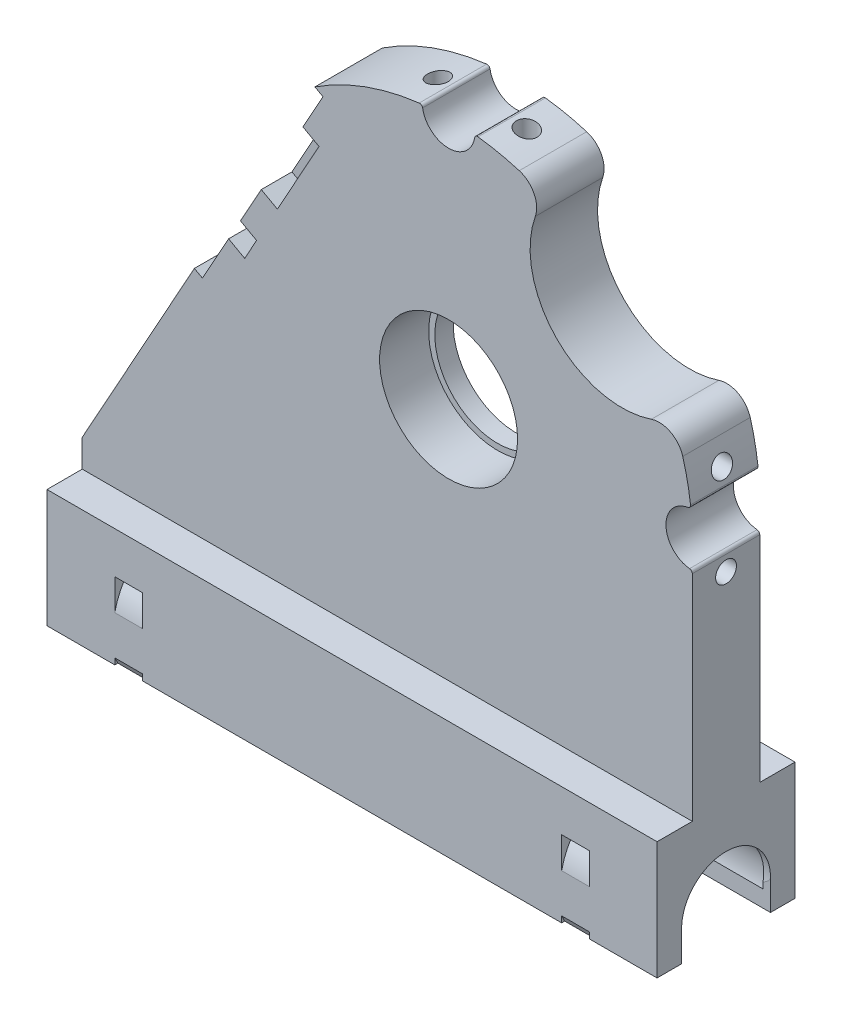
SolidWorks part; units mm, degrees
ref_plane "Alzado" through (0, 0, 0) normal (0, 0, 1) x (1, 0, 0)
ref_plane "Planta" through (0, 0, 0) normal (0, 1, 0) x (1, 0, 0)
ref_plane "Vista lateral" through (0, 0, 0) normal (1, 0, 0) x (0, 0, -1)
sketch "Croquis1" plane through (0, 0, 0) normal (0, 0, 1) x (1, 0, 0)
  line L1 (-25.8795, 44.4694) -> (-23.2553, 43.0157)
  line L2 (-23.2553, 43.0157) -> (-21.3161, 46.5141)
  line L3 (-21.3161, 46.5141) -> (-23.9399, 47.9686)
  line L5 (-20.5463, 54.0909) -> (-17.9224, 52.6365)
  line L6 (-17.9224, 52.6365) -> (-11.1351, 64.8812)
  line L7 (-11.1351, 64.8812) -> (-13.7589, 66.3356)
  line L8 (-11.7988, 72.9658) -> (-10.4868, 72.2386)
  line L17 (-10.4868, 72.2386) -> (-30.1459, 36.7728)
  line L18 (-30.1459, 36.7728) -> (-31.4578, 37.5)
  line L19 (-31.4578, 37.5) -> (-49.75, 4.5)
  line L20 (49.75, 0) -> (49.75, 34.9761)
  line L22 (-49.75, 4.5) -> (-49.75, 0)
  line L23 (-49.75, 0) -> (49.75, 0)
  line L25 (40.7, 29.375) -> (40.7, 35.625)
  line L26 (43.55, 29.375) -> (43.55, 35.625)
  line L27 (43.55, 29.375) -> (40.7, 29.375)
  line L28 (43.55, 35.625) -> (40.7, 35.625)
  line L29 (43.55, 43.875) -> (40.7, 43.875)
  line L30 (40.7, 50.125) -> (40.7, 43.875)
  line L31 (43.55, 50.125) -> (43.55, 43.875)
  line L32 (43.55, 50.125) -> (40.7, 50.125)
  line L33 (20.375, 70.44) -> (14.125, 70.44)
  line L34 (20.375, 70.44) -> (20.375, 73.29)
  line L35 (20.375, 73.29) -> (14.125, 73.29)
  line L36 (14.125, 70.44) -> (14.125, 73.29)
  line L37 (-0.375, 73.29) -> (-0.375, 70.44)
  line L38 (5.875, 70.44) -> (-0.375, 70.44)
  line L39 (5.875, 73.29) -> (5.875, 70.44)
  line L40 (5.875, 73.29) -> (-0.375, 73.29)
  arc A0 (49.4597, 44.5454) -> (14.7954, 79.2097) centre (10, 39.75) ccw
  arc A1 (14.7954, 79.2097) -> (14.2419, 78.7953) centre (14.7351, 78.7133) ccw
  arc A2 (5.7611, 78.7776) -> (14.2419, 78.7953) centre (10, 79.5) ccw
  arc A3 (5.7611, 78.7776) -> (5.2079, 79.19) centre (5.2682, 78.6936) ccw
  arc A4 (5.2079, 79.19) -> (-11.7988, 72.9658) centre (10, 39.75) ccw
  arc A5 (49.75, 34.9761) -> (49.3021, 35.4734) centre (49.25, 34.9761) ccw
  arc A6 (49.0453, 43.9919) -> (49.3021, 35.4734) centre (49.75, 39.75) ccw
  arc A7 (49.0453, 43.9919) -> (49.4597, 44.5454) centre (48.9633, 44.4851) ccw
  circle A8 centre (10, 39.75) radius 11.25
  circle A11 centre (10, 39.75) radius 10.25
  point P30 (10, 59.75)
  point P65 (5.875, 71.865)
  dimension "D2" = 22.5
  dimension "D7" = 4.3
  dimension "D8" = 0.5
  dimension "D9" = 0.5
  dimension "D10" = 39.75
  dimension "D11" = 4.3
  dimension "D25" = 0.5
  dimension "D26" = 0.5
  dimension "D36" = 20.5
  dimension "D37" = 40.55
  dimension "D4" = 6.25
  dimension "D5" = 2.85
  dimension "D6" = 2.85
  dimension "D12" = 39.75
  dimension "D13" = 10
  dimension "D14" = 99.5
  dimension "D15" = 33
  dimension "D16" = 61
  dimension "D17" = 1.5
  dimension "D18" = 90
  dimension "D19" = 4
  dimension "D20" = 3
  dimension "D21" = 8.8
  dimension "D22" = 7
  dimension "D23" = 14
  dimension "D24" = 1.5
  dimension "D27" = 39.75
  dimension "D29" = 8.25
  dimension "D30" = 8.25
  dimension "D31" = 33.54
  dimension "D32" = 4.125
  dimension "D33" = 30.7
  dimension "D34" = 4.125
  dimension "D35" = 39.75
  dimension "D38" = 33.2158
  dimension "D39" = 25.1312
  dimension "D40" = 31.3161
  dimension "D41" = 3.2657
extrude "Saliente-Extruir1" add sketch "Croquis1" against normal blind 11 contours L7 L17 L5 L6 | L3 L17 L1 L2 | A8 A11 | A6 A7 A0 A1 A2 A3 A4 L8 L17 L7 L6 L5 L3 L2 L1 L18 L19 L22 L23 L20 A5 A8 L33 L36 L35 L34 L28 L26 L27 L25 L32 L31 L29 L30 L40 L39 L38 L37 region at (-23.5978, 45.492, 0) region at (-25.1837, 42.63, 0) region at (-15.8407, 59.486, 0) region at (-0.9318, 39.75, 0)
extrude "Cortar-Extruir1" cut sketch "Croquis1<8>" against normal blind 8 contours A8
sketch "Croquis1<8>" plane through (0, 0, 0) normal (0, 0, 1) x (1, 0, 0) same geometry as "Croquis1"
extrude "Cortar-Extruir2" cut sketch "Croquis1<9>" against normal blind 5 contours L7 L17 L5 L6 | L3 L17 L1 L2 region at (-23.5978, 45.492, 0) region at (-15.8407, 59.486, 0)
sketch "Croquis1<9>" plane through (0, 0, 0) normal (0, 0, 1) x (1, 0, 0) same geometry as "Croquis1"
sketch "Croquis3" plane through (40.7, 0, 0) normal (1, 0, 0) x (0, 0, -1)
  line L0 (11, 50.125) -> (11, 43.875) construction
  line L2 (11, 44.5454) -> (0, 44.5454) construction
  line L4 (11, 29.375) -> (11, 35.625) construction
  circle A0 centre (5.5, 47) radius 1.7
  circle A1 centre (5.5, 32.5) radius 1.7
  point P6 (11, 47)
  point P11 (5.5, 44.5454)
  point P15 (11, 32.5)
  dimension "D1" = 3.4
  dimension "D2" = 3.4
extrude "Cortar-Extruir3" cut sketch "Croquis3" along normal through all and the other way blind 10.95 contours A0 | A1
sketch "Croquis4" plane through (0, 0, -11) normal (0, 0, -1) x (-1, 0, 0)
  line L0 (-49.75, 10) -> (49.75, 10)
  line L3 (49.75, 0) -> (-49.75, 0) construction
  line L11 (30.1459, 36.7728) -> (10.4868, 72.2386)
  line L12 (10.4868, 72.2386) -> (11.7988, 72.9658)
  line L13 (-49.75, 34.9761) -> (-49.75, 0)
  line L14 (-49.75, 0) -> (49.75, 0)
  line L15 (49.75, 0) -> (49.75, 4.5)
  line L16 (49.75, 4.5) -> (31.4578, 37.5)
  line L17 (31.4578, 37.5) -> (30.1459, 36.7728)
  line L18 (30.1459, 36.7728) -> (10.4868, 72.2386)
  line L19 (10.4868, 72.2386) -> (11.7988, 72.9658)
  line L20 (-49.75, 34.9761) -> (-49.75, 0)
  line L21 (-49.75, 0) -> (49.75, 0)
  line L22 (49.75, 0) -> (49.75, 4.5)
  line L23 (49.75, 4.5) -> (31.4578, 37.5)
  line L24 (31.4578, 37.5) -> (30.1459, 36.7728)
  arc A8 (11.7988, 72.9658) -> (-5.2079, 79.19) centre (-10, 39.75) ccw
  arc A9 (-5.2079, 79.19) -> (-5.7611, 78.7776) centre (-5.2682, 78.6936) ccw
  arc A10 (-14.2419, 78.7953) -> (-5.7611, 78.7776) centre (-10, 79.5) ccw
  arc A11 (-14.2419, 78.7953) -> (-14.7954, 79.2097) centre (-14.7351, 78.7133) ccw
  arc A12 (-14.7954, 79.2097) -> (-49.4597, 44.5454) centre (-10, 39.75) ccw
  arc A13 (-49.4597, 44.5454) -> (-49.0453, 43.9919) centre (-48.9633, 44.4851) ccw
  arc A14 (-49.3021, 35.4734) -> (-49.0453, 43.9919) centre (-49.75, 39.75) ccw
  arc A15 (-49.3021, 35.4734) -> (-49.75, 34.9761) centre (-49.25, 34.9761) ccw
  arc A16 (11.7988, 72.9658) -> (-5.2079, 79.19) centre (-10, 39.75) ccw
  arc A17 (-5.2079, 79.19) -> (-5.7611, 78.7776) centre (-5.2682, 78.6936) ccw
  arc A18 (-14.2419, 78.7953) -> (-5.7611, 78.7776) centre (-10, 79.5) ccw
  arc A19 (-14.2419, 78.7953) -> (-14.7954, 79.2097) centre (-14.7351, 78.7133) ccw
  arc A20 (-14.7954, 79.2097) -> (-49.4597, 44.5454) centre (-10, 39.75) ccw
  arc A21 (-49.4597, 44.5454) -> (-49.0453, 43.9919) centre (-48.9633, 44.4851) ccw
  arc A22 (-49.3021, 35.4734) -> (-49.0453, 43.9919) centre (-49.75, 39.75) ccw
  arc A23 (-49.3021, 35.4734) -> (-49.75, 34.9761) centre (-49.25, 34.9761) ccw
  dimension "D1" = 10
  dimension "D2" = 0
sketch "Croquis5" plane through (0, 70.44, 0) normal (0, 1, 0) x (1, 0, 0)
  line L0 (5.875, 0) -> (-0.375, 0) construction
  line L1 (20.375, 0) -> (14.125, 0) construction
  line L2 (14.7954, 11) -> (14.7954, 0) construction
  circle A0 centre (17.25, 5.5) radius 1.7
  circle A1 centre (2.75, 5.5) radius 1.7
  point P7 (2.75, 0)
  point P10 (17.25, 0)
  point P14 (14.7954, 5.5)
  dimension "D1" = 3.4
extrude "Cortar-Extruir4" cut sketch "Croquis5" along normal through all and the other way blind 10 contours A0 | A1
sketch "Croquis9" plane through (0, 70.44, 0) normal (0, 1, 0) x (1, 0, 0)
  line L0 (14.125, 0) -> (20.375, 0) construction
  line L1 (14.1323, 7.3) -> (14.1323, 3.7)
  line L2 (14.125, 3.7042) -> (17.25, 1.9)
  line L3 (17.25, 1.9) -> (20.375, 3.7042)
  line L4 (20.3677, 3.7) -> (20.3677, 7.3)
  line L5 (20.3677, 7.3) -> (17.25, 9.1)
  line L6 (17.25, 9.1) -> (14.1323, 7.3)
  line L7 (-0.3677, 7.3) -> (-0.3677, 3.7)
  line L8 (-0.375, 3.7042) -> (2.75, 1.9)
  line L9 (2.75, 1.9) -> (5.875, 3.7042)
  line L10 (5.8677, 3.7) -> (5.8677, 7.3)
  line L11 (5.8677, 7.3) -> (2.75, 9.1)
  line L12 (2.75, 9.1) -> (-0.3677, 7.3)
  line L13 (20.375, 0) -> (20.375, 11) construction
  line L14 (20.375, 11) -> (14.125, 11) construction
  line L15 (14.125, 11) -> (14.125, 0) construction
  line L16 (-0.375, 0) -> (5.875, 0) construction
  line L17 (5.875, 0) -> (5.875, 11) construction
  line L18 (5.875, 11) -> (-0.375, 11) construction
  line L19 (-0.375, 11) -> (-0.375, 0) construction
  line L20 (14.125, 0) -> (20.375, 0)
  line L21 (20.375, 0) -> (20.375, 11)
  line L22 (20.375, 11) -> (14.125, 11)
  line L23 (14.125, 11) -> (14.125, 0)
  line L24 (-0.375, 0) -> (5.875, 0)
  line L25 (5.875, 0) -> (5.875, 11)
  line L26 (5.875, 11) -> (-0.375, 11)
  line L27 (-0.375, 11) -> (-0.375, 0)
  circle A0 centre (17.25, 5.5) radius 3.1177 construction
  circle A1 centre (2.75, 5.5) radius 3.1177 construction
  line M7 (14.125, 0) -> (20.375, 0)
  line M8 (20.375, 0) -> (20.375, 11)
  line M10 (14.125, 11) -> (14.125, 0)
  dimension "D3" = 6.2354
  dimension "D4" = 6.2354
  dimension "D1" = 3.6
  dimension "D2" = 3.6
extrude "Saliente-Extruir8" add sketch "Croquis9" along normal up to vertex (2.85 mm away) contours L3 L2 M10 M7 M8 | L8 L27 L24 L25 L9 region at (17.25, 70.44, -1.4495) region at (2.75, 70.44, -1.4495) up to point (-0.375, 73.29, 0)
sketch "Croquis11" plane through (40.7, 0, 0) normal (1, 0, 0) x (0, 0, -1)
  line L0 (0, 35.625) -> (0, 29.375) construction
  line L1 (9.1, 47) -> (7.3, 50.1177)
  line L2 (7.3, 50.1177) -> (3.7, 50.1177)
  line L3 (3.7042, 50.125) -> (1.9, 47)
  line L4 (1.9, 47) -> (3.7042, 43.875)
  line L5 (3.7, 43.8823) -> (7.3, 43.8823)
  line L6 (7.3, 43.8823) -> (9.1, 47)
  line L7 (9.1, 32.5) -> (7.3, 35.6177)
  line L8 (7.3, 35.6177) -> (3.7, 35.6177)
  line L9 (3.7042, 35.625) -> (1.9, 32.5)
  line L10 (1.9, 32.5) -> (3.7042, 29.375)
  line L11 (3.7, 29.3823) -> (7.3, 29.3823)
  line L12 (7.3, 29.3823) -> (9.1, 32.5)
  line L13 (0, 29.375) -> (11, 29.375) construction
  line L14 (11, 29.375) -> (11, 35.625) construction
  line L15 (11, 35.625) -> (0, 35.625) construction
  line L16 (0, 50.125) -> (0, 43.875) construction
  line L17 (0, 43.875) -> (11, 43.875) construction
  line L18 (11, 43.875) -> (11, 50.125) construction
  line L19 (11, 50.125) -> (0, 50.125) construction
  line L20 (0, 35.625) -> (0, 29.375)
  line L21 (0, 29.375) -> (11, 29.375)
  line L22 (11, 29.375) -> (11, 35.625)
  line L23 (11, 35.625) -> (0, 35.625)
  line L24 (0, 50.125) -> (0, 43.875)
  line L25 (0, 43.875) -> (11, 43.875)
  line L26 (11, 43.875) -> (11, 50.125)
  line L27 (11, 50.125) -> (0, 50.125)
  circle A0 centre (5.5, 47) radius 3.1177 construction
  circle A1 centre (5.5, 32.5) radius 3.1177 construction
  line M6 (0, 50.125) -> (0, 43.875)
  line M7 (0, 43.875) -> (11, 43.875)
  line M9 (11, 50.125) -> (0, 50.125)
  dimension "D3" = 6.2354
  dimension "D4" = 6.2354
  dimension "D1" = 3.6
  dimension "D2" = 3.6
extrude "Saliente-Extruir9" add sketch "Croquis11" along normal up to vertex (2.85 mm away) contours L9 L23 L20 L21 L10 | L4 L3 M9 M6 M7 region at (40.7, 47, -1.4495) region at (40.7, 32.5, -1.4495) up to point (43.55, 35.625, -11)
sketch "Croquis12" plane through (0, 0, 0) normal (1, 0, 0) x (0, 0, -1)
  line L0 (-1.75, -19.25) -> (-5.75, -19.25)
  line L1 (5.5, -14.25) -> (5.5, -24.3396) construction
  line L2 (-1.75, -14.25) -> (-1.75, -19.25)
  line L3 (12.75, -19.25) -> (12.75, -14.25)
  line L4 (12.75, -19.25) -> (16.75, -19.25)
  line L5 (16.75, -19.25) -> (16.75, 0)
  line L6 (-5.75, 0) -> (16.75, 0)
  line L7 (-5.75, -19.25) -> (-5.75, 0)
  line L8 (11, 0) -> (0, 0) construction
  arc A0 (12.75, -14.25) -> (-1.75, -14.25) centre (5.5, -14.25) ccw
  point P10 (5.5, 0)
  point P11 (5.5, 0)
  dimension "D1" = 7.25
  dimension "D2" = 19.25
  dimension "D3" = 5
  dimension "D4" = 4
  dimension "D5" = 14.5
extrude "Saliente-Extruir10" add sketch "Croquis12" against normal up to surface and the other way up to surface up to face at (-49.75, 2.25, -5.5) other way up to face at (49.75, 34.2, -5.5)
ref_plane "Plano1" through (0, -14.25, 0) normal (0, 1, 0) x (1, 0, 0)
sketch "Croquis13" plane through (0, -14.25, 0) normal (0, 1, 0) x (1, 0, 0)
  line L0 (-23.134, -1.75) -> (-23.134, 5.5)
  line L1 (-23.134, 5.5) -> (-49.75, 5.5)
  line L2 (-49.75, 5.5) -> (-49.75, -1.75)
  line L3 (-49.75, -1.75) -> (-48.542, -1.8639)
  line L4 (-48.542, -1.8639) -> (-48.542, -2.1)
  line L5 (-48.542, -2.1) -> (-24.342, -2.1)
  line L6 (-24.342, -2.1) -> (-24.342, -1.8639)
  line L7 (-24.342, -1.8639) -> (-23.134, -1.75)
  line L8 (-23.134, 5.5) -> (-49.75, 5.5) construction
  line L9 (-49.75, 5.5) -> (49.75, 5.5) construction
  line L10 (-49.75, 12.75) -> (-49.75, -1.75) construction
  line L11 (-49.75, -1.75) -> (49.75, -1.75) construction
  point P8 (-36.5275, 41.7092)
  point P9 (-36.442, 5.5)
  point P12 (-36.442, -2.1)
  point P13 (-49.75, 5.5)
  dimension "D1" = 7.25
  dimension "D2" = 7.25
  dimension "D3" = 0.2361
  dimension "D4" = 1.208
  dimension "D5" = 24.2
  dimension "D6" = 26.616
  dimension "D7" = 0.2361
  dimension "D8" = 7.25
  dimension "D9" = 7.6
revolve "Cortar-Revolución1" cut sketch "Croquis13" angle 360 about L1
mirror "Simetría1" about plane through (0, 0, 0) normal (1, 0, 0) of "Cortar-Revolución1"
ref_plane "Plano2" through (-36.442, 0, 0) normal (1, 0, 0) x (0, 0, -1)
sketch "Croquis14" plane through (-36.442, 0, 0) normal (1, 0, 0) x (0, 0, -1)
  line L0 (-5.75, -6.7876) -> (-5.75, -11.8652)
  line L1 (16.75, -11.8652) -> (16.75, -6.7876)
  line L2 (16.75, -18.25) -> (16.25, -19.25)
  line L3 (16.75, -18.25) -> (16.75, -19.25)
  line L4 (16.75, -19.25) -> (16.25, -19.25)
  line L5 (5.5, -14.25) -> (5.5, -15.1053) construction
  line L6 (-5.75, -19.25) -> (-5.25, -19.25)
  line L7 (-5.75, -18.25) -> (-5.75, -19.25)
  line L8 (-5.75, -18.25) -> (-5.25, -19.25)
  line L9 (-5.75, 0) -> (-5.75, -19.25) construction
  line L10 (-5.75, -19.25) -> (-1.75, -19.25) construction
  arc A0 (-5.75, -11.8652) -> (16.75, -11.8652) centre (5.5, -14.25) cw
  arc A1 (16.75, -6.7876) -> (-5.75, -6.7876) centre (5.5, -14.25) ccw
  arc A2 (12.75, -14.25) -> (-1.75, -14.25) centre (5.5, -14.25) ccw construction
  point P12 (47.1143, -17.5257)
  dimension "D1" = 11.5
  dimension "D2" = 13.5
  dimension "D3" = 5.0776
  dimension "D4" = 0.5
  dimension "D5" = 1
extrude "Cortar-Extruir5" cut sketch "Croquis14" against normal mid plane 4.5 contours L4 L3 L2 | L8 L7 L6 | L1 A1 L0 A0 region at (-36.442, -18.9167, -16.5833) region at (-36.442, -18.9167, 5.5833)
mirror "Simetría2" about plane through (0, 0, 0) normal (1, 0, 0) of "Cortar-Extruir5"
sketch "Croquis15" plane through (0, 0, -16.75) normal (0, 0, -1) x (-1, 0, 0)
  line L0 (-16, 0) -> (16, 0)
  line L1 (-16, 0) -> (-16, -19.25)
  line L2 (-16, -19.25) -> (16, -19.25)
  line L3 (16, 0) -> (16, -19.25)
  line L4 (-16, 0) -> (16, -19.25) construction
  line L5 (-16, -19.25) -> (16, 0) construction
  line L6 (49.75, 0) -> (-49.75, 0) construction
  line L7 (34.192, -19.25) -> (-34.192, -19.25) construction
  point P0 (0, -9.625)
  dimension "D1" = 32
extrude "Saliente-Extruir11" add sketch "Croquis15" along normal blind 18.6
ref_plane "Plano3" through (-12.8, 0, 0) normal (-1, 0, 0) x (0, 0, 1)
sketch "Croquis16" plane through (-12.8, 0, 0) normal (-1, 0, 0) x (0, 0, 1)
  line L0 (-21.5505, -3.043) -> (-35.35, -3.043)
  line L1 (-35.35, -3.043) -> (-35.35, -16.207)
  line L2 (-35.35, -16.207) -> (-21.5505, -16.207)
  line L3 (-21.5505, -16.207) -> (-17.7504, -9.625)
  line L4 (-17.7504, -9.625) -> (-21.5505, -3.043)
  line L5 (-35.35, -5.125) -> (-25.35, -5.125)
  line L6 (-25.35, -14.125) -> (-35.35, -14.125)
  line L7 (-35.35, -14.125) -> (-35.35, -16.2105)
  line L8 (-35.35, -16.2105) -> (-21.55, -16.2105)
  line L9 (-21.55, -16.2105) -> (-17.7504, -9.6285)
  line L10 (-17.7504, -9.6285) -> (-21.55, -3.0465)
  line L11 (-21.55, -3.0465) -> (-35.35, -3.0465)
  line L12 (-35.35, -3.0465) -> (-35.35, -5.125)
  line L13 (-35.35, -19.25) -> (-35.35, 0) construction
  arc A0 (-25.35, -14.125) -> (-25.35, -5.125) centre (-25.35, -9.625) ccw
  point P5 (-35.35, -9.625)
  point P19 (-35.35, -9.625)
  dimension "D4" = 4.5
  dimension "D1" = 13.164
  dimension "D2" = 17.5996
  dimension "D3" = 120
  dimension "D5" = 10
  dimension "D6" = 10
extrude "Cortar-Extruir6" cut sketch "Croquis16" against normal through all both and the other way through all contours A0 L6 L1 L2 L3 L10 L11 L5 | L6 A0 L5 L1 region at (-12.8, -3.2663, -28.45) region at (-12.8, -9.625, -28.5456)
extrude "Saliente-Extruir12" add sketch "Croquis16<3>" against normal blind 2.9 contours A0 L6 L1 L2 L3 L10 L11 L5 region at (-12.8, -3.2663, -28.45)
sketch "Croquis16<3>" plane through (-12.8, 0, 0) normal (-1, 0, 0) x (0, 0, 1) same geometry as "Croquis16"
sketch "Croquis17" plane through (-9.9, 0, 0) normal (1, 0, 0) x (0, 0, -1)
  line L0 (25.35, -1.425) -> (35.35, -1.425)
  line L1 (35.35, -17.825) -> (25.35, -17.825)
  line L2 (35.35, -1.425) -> (35.35, -5.125)
  line L3 (35.35, -14.125) -> (35.35, -17.825)
  line L4 (35.35, -17.825) -> (35.2517, -17.8186)
  line L5 (25.35, -14.125) -> (35.35, -14.125) construction
  line L6 (35.35, -5.125) -> (25.35, -5.125) construction
  line L7 (25.35, -14.125) -> (35.35, -14.125)
  line L8 (35.35, -5.125) -> (25.35, -5.125)
  arc A0 (25.35, -1.425) -> (25.35, -17.825) centre (25.35, -9.625) ccw
  arc A1 (25.35, -5.125) -> (25.35, -14.125) centre (25.35, -9.625) ccw
  arc A2 (25.35, -5.125) -> (25.35, -14.125) centre (25.35, -9.625) ccw construction
  dimension "D1" = 8.2
  dimension "D2" = 16.4
  dimension "D3" = 10
extrude "Cortar-Extruir9" cut sketch "Croquis17" along normal blind 2.2 contours L1 A0 L0 L2 L8 A1 L7 L3
sketch "Croquis18" plane through (0, 0, 0) normal (0, 0, 1) x (1, 0, 0)
  circle A0 centre (38.292, 67.6718) radius 15
  arc A1 (49.4597, 44.5454) -> (14.7954, 79.2097) centre (10, 39.75) ccw construction
  dimension "D1" = 30
extrude "Cortar-Extruir10" cut sketch "Croquis18" against normal through all
fillet "Redondeo1" radius 4 2 edges at (46.6249, 55.1993, -5.5) (25.9303, 76.1682, -5.5)
extrude "Cortar-Extruir11" cut sketch "Croquis1<10>" against normal blind 9 contours L3 L17 L1 L2 region at (-23.5978, 45.492, 0)
sketch "Croquis1<10>" plane through (0, 0, 0) normal (0, 0, 1) x (1, 0, 0) same geometry as "Croquis1"
sketch "Croquis19" plane through (-38.6529, 21.4257, 0) normal (-0.8746, 0.4848, 0) x (0, 0, 1)
  line L0 (-9, 30.3479) -> (0, 30.3479) construction
  line L1 (-11, 58.0972) -> (-11, 17.5472) construction
  circle A0 centre (-8, 35.3479) radius 1.7
  circle A1 centre (-8, 54.0979) radius 1.7
  dimension "D1" = 3.4
  dimension "D3" = 3
  dimension "D4" = 3.4
  dimension "D5" = 18.75
  dimension "D2" = 5
extrude "Cortar-Extruir12" cut sketch "Croquis19" against normal blind 17 contours A0 | A1 region at (-21.5159, 52.3417, -8)
ref_plane "Plano4" through (-33.93, 18.8077, 0) normal (-0.8746, 0.4848, 0) x (0, 0, 1)
sketch "Croquis20" plane through (-33.93, 18.8077, 0) normal (-0.8746, 0.4848, 0) x (0, 0, 1)
  line L0 (-8, 57.6979) -> (-11, 57.6979)
  line L1 (-4.8823, 52.2979) -> (-4.8823, 55.8979)
  line L2 (-4.8823, 55.8979) -> (-8, 57.6979)
  line L3 (-8, 57.6979) -> (-11.1177, 55.8979)
  line L4 (-11.1177, 55.8979) -> (-11.1177, 52.2979)
  line L5 (-11.1177, 52.2979) -> (-8, 50.4979)
  line L6 (-8, 50.4979) -> (-4.8823, 52.2979)
  line L7 (-8, 31.7479) -> (-4.8823, 33.5479)
  line L8 (-4.8823, 33.5479) -> (-4.8823, 37.1479)
  line L9 (-4.8823, 37.1479) -> (-8, 38.9479)
  line L10 (-8, 38.9479) -> (-11.1177, 37.1479)
  line L11 (-11.1177, 37.1479) -> (-11.1177, 33.5479)
  line L12 (-11.1177, 33.5479) -> (-8, 31.7479)
  line L13 (-8, 50.4979) -> (-11, 50.4979)
  line L14 (-8, 38.9479) -> (-11, 38.9479)
  line L15 (-8, 31.7479) -> (-11, 31.7479)
  line L16 (-11, 58.0972) -> (-11, 17.5472) construction
  line L17 (-11, 58.0972) -> (-11, 17.5472)
  circle A0 centre (-8, 54.0979) radius 3.1177 construction
  circle A1 centre (-8, 35.3479) radius 3.1177 construction
  dimension "D1" = 3.6
extrude "Cortar-Extruir13" cut sketch "Croquis20" along normal blind 2.8 contours L0 L17 L3 | L3 L17 L5 L6 L1 L2 | L5 L17 L13 | L10 L17 L12 L7 L8 L9 | L14 L17 L10 | L12 L17 L15 region at (-6.2374, 68.7665, -10) region at (-15.3275, 52.3674, -10) region at (-7.7028, 66.1228, -7.9603) region at (-9.1682, 63.4792, -10) region at (-16.7929, 49.7237, -7.9603) region at (-18.2584, 47.08, -10)
